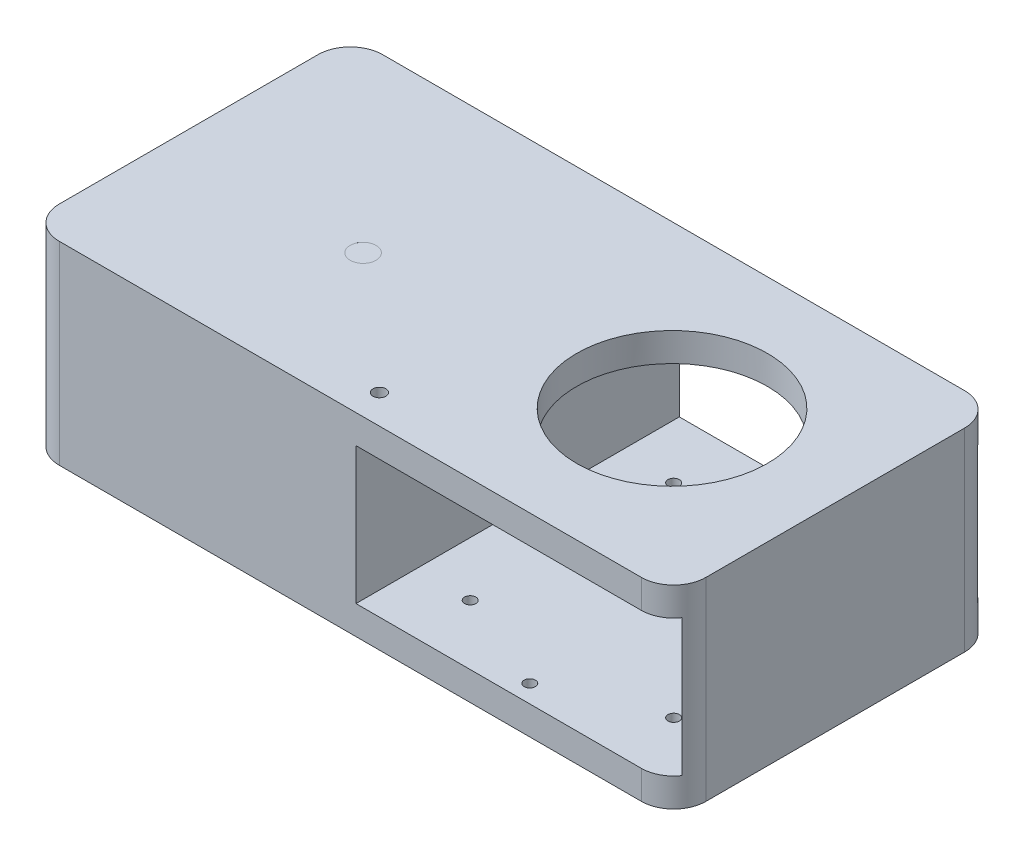
SolidWorks part; units mm, degrees
ref_plane "前视基准面" through (0, 0, 0) normal (0, 0, 1) x (1, 0, 0)
ref_plane "上视基准面" through (0, 0, 0) normal (0, 1, 0) x (1, 0, 0)
ref_plane "右视基准面" through (0, 0, 0) normal (1, 0, 0) x (0, 0, -1)
sketch "草图1" plane through (0, 0, 0) normal (0, 1, 0) x (1, 0, 0)
  line L1 (-100, 50) -> (100, 50)
  line L2 (-100, 50) -> (-100, -50)
  line L3 (-100, -50) -> (100, -50)
  line L4 (100, 50) -> (100, -50)
  line L5 (-100, 50) -> (100, -50) construction
  line L6 (-100, -50) -> (100, 50) construction
  point P0 (0, 0)
  dimension "D1" = 200
  dimension "D2" = 100
extrude "凸台-拉伸2" add sketch "草图1" along normal blind 60
sketch "草图3" plane through (0, 60, 0) normal (0, 1, 0) x (1, 0, 0)
  line L0 (0, 0) -> (99.0015, 0) construction
  line L1 (0, 0) -> (-100, 0) construction
  line L2 (-100, 50) -> (-100, -50) construction
  line L3 (0, 0) -> (0, 50) construction
  line L4 (100, 50) -> (-100, 50) construction
  line L5 (0, 0) -> (0, -50) construction
  line L6 (-100, -50) -> (100, -50) construction
  circle A0 centre (49.5008, 0) radius 48.25 construction
  circle A1 centre (-49.5008, 0) radius 48.25 construction
  circle A16 centre (50.1748, 17.2368) radius 2
  circle A17 centre (64.7653, 8.0346) radius 2
  circle A18 centre (64.0913, -9.2022) radius 2
  circle A19 centre (48.8267, -17.2368) radius 2
  circle A20 centre (34.2362, -8.0346) radius 2
  circle A21 centre (34.9103, 9.2022) radius 2
  circle A23 centre (-64.7653, 8.0346) radius 2
  circle A24 centre (-64.0913, -9.2022) radius 2
  circle A25 centre (-48.8267, -17.2368) radius 2
  circle A26 centre (-34.2362, -8.0346) radius 2
  circle A27 centre (-34.9103, 9.2022) radius 2
  circle A28 centre (-50.1748, 17.2368) radius 2
  point P31 (49.5008, 0)
  point P34 (49.5008, 0)
  dimension "D1" = 96.5
  dimension "D3" = 6
sketch "草图4" plane through (0, 0, -50) normal (0, 0, -1) x (-1, 0, 0)
  line L0 (-100, 60) -> (-100, 0) construction
  line L1 (-100, 30) -> (100, 30) construction
  line L2 (100, 60) -> (100, 0) construction
  line L3 (0, 30) -> (0, 0) construction
  line L4 (0, 30) -> (0, 60) construction
  line L5 (-100, 60) -> (100, 60) construction
  line L6 (-100, 0) -> (-100, 60)
  line L7 (-100, 60) -> (0, 60)
  line L8 (0, 60) -> (0, 0) construction
  line L9 (0, 0) -> (-100, 0)
  line L10 (-50, 60) -> (-50, 0) construction
  line L12 (-98.25, 51.15) -> (-1.75, 51.15)
  line L13 (-98.25, 51.15) -> (-98.25, 8.85)
  line L14 (-98.25, 8.85) -> (-1.75, 8.85)
  line L15 (-1.75, 51.15) -> (-1.75, 8.85)
  line L16 (-98.25, 51.15) -> (-1.75, 8.85) construction
  line L17 (-98.25, 8.85) -> (-1.75, 51.15) construction
  point P16 (-50, 30)
  dimension "D1" = 42.3
  dimension "D2" = 96.5
extrude "切除-拉伸7" cut sketch "草图4" against normal blind 180 contours L15 L12 L13 L14 region at (50, 30, -50)
sketch "草图6" plane through (0, 60, 0) normal (0, 1, 0) x (1, 0, 0)
  line L0 (0, 0) -> (-100, 0) construction
  line L1 (-100, 50) -> (-100, -50) construction
  circle A0 centre (-50, 0) radius 2
sketch "草图9" plane through (0, 60, 0) normal (0, 1, 0) x (1, 0, 0)
  line L0 (100, 0) -> (-1.1108, 0) construction
  line L1 (100, -50) -> (100, 50) construction
  circle A0 centre (49.4446, 0) radius 2
sketch "草图10" plane through (0, 60, 0) normal (0, 1, 0) x (1, 0, 0)
  line L0 (0, 0) -> (0, -50) construction
  line L1 (-100, -50) -> (100, -50) construction
  line L2 (0, -50) -> (0, -41) construction
  circle A0 centre (0, -41) radius 2
extrude "切除-拉伸12" cut sketch "草图10" against normal blind 3
sketch "草图11" plane through (0, 0, -50) normal (0, 0, -1) x (-1, 0, 0)
  line L0 (100, 30) -> (-1.75, 30) construction
  line L1 (100, 60) -> (100, 0) construction
  line L2 (-1.75, 51.15) -> (-1.75, 8.85) construction
  line L3 (49.125, 30) -> (49.125, 0) construction
  line L4 (-100, 0) -> (100, 0) construction
  circle A0 centre (49.125, 30) radius 2
sketch "草图12" plane through (0, 0, -50) normal (0, 0, -1) x (-1, 0, 0)
  line L0 (100, 30) -> (-100, 30) construction
  line L1 (-100, 60) -> (-100, 0) construction
  line L2 (0, 60) -> (0, 0) construction
  line L3 (-100, 60) -> (100, 60) construction
  circle A0 centre (0, 30) radius 1
  dimension "D1" = 2
extrude "切除-拉伸13" cut sketch "草图12" against normal blind 3 contours A0
sketch "草图15" plane through (0, 0, -50) normal (0, 0, -1) x (-1, 0, 0)
  line L0 (-98.25, 51.15) -> (-98.25, 60)
  line L1 (0, 60) -> (-99.0015, 60) construction
sketch "草图16" plane through (0, 60, 0) normal (0, 1, 0) x (1, 0, 0)
  line L0 (0, 0) -> (99.0015, 0) construction
  circle A0 centre (49.5008, 0) radius 29.5
  dimension "D1" = 59
extrude "切除-拉伸14" cut sketch "草图16" against normal blind 16
sketch "草图17" plane through (0, 8.85, 0) normal (0, 1, 0) x (1, 0, 0)
  line L0 (50, 50) -> (50, -50) construction
  line L1 (98.25, 50) -> (1.75, 50) construction
  line L2 (98.25, -50) -> (1.75, -50) construction
  line L3 (98.25, 50) -> (98.25, -50) construction
  line L4 (98.25, 0) -> (50, 0) construction
  circle A0 centre (50, 0) radius 44.5 construction
  circle A1 centre (50, -44.5) radius 1.75
  circle A2 centre (18.5337, -31.4663) radius 1.75
  circle A3 centre (5.5, 0) radius 1.75
  circle A4 centre (18.5337, 31.4663) radius 1.75
  circle A5 centre (50, 44.5) radius 1.75
  circle A6 centre (81.4663, 31.4663) radius 1.75
  circle A7 centre (94.5, 0) radius 1.75
  circle A8 centre (81.4663, -31.4663) radius 1.75
  point P31 (50, 0)
  dimension "D1" = 3.5
  dimension "D2" = 8
extrude "切除-拉伸15" cut sketch "草图17" against normal blind 10
sketch "草图22" plane through (0, 60, 0) normal (0, 1, 0) x (1, 0, 0)
  circle A0 centre (-39.9438, -6.1151) radius 4
extrude "切除-拉伸16" cut sketch "草图22" against normal blind 0.001 contours A0
fillet "圆角1" radius 10 1 edges at (-100, 30, -50) type face fillet first side face at (-1, 30, -50) second side face at (-100, 30, 0)
fillet "圆角2" radius 10 1 edges at (-100, 30, 50) type face fillet first side face at (-100, 30, 5) second side face at (0, 30, 50)
fillet "圆角3" radius 10 1 edges at (100, 30, 50) type face fillet first side face at (5, 30, 50) second side face at (100, 30, 0)
fillet "圆角4" radius 10 1 edges at (100, 30, -50) type face fillet first side face at (100, 30, -5) second side face at (-1, 30, -50)
